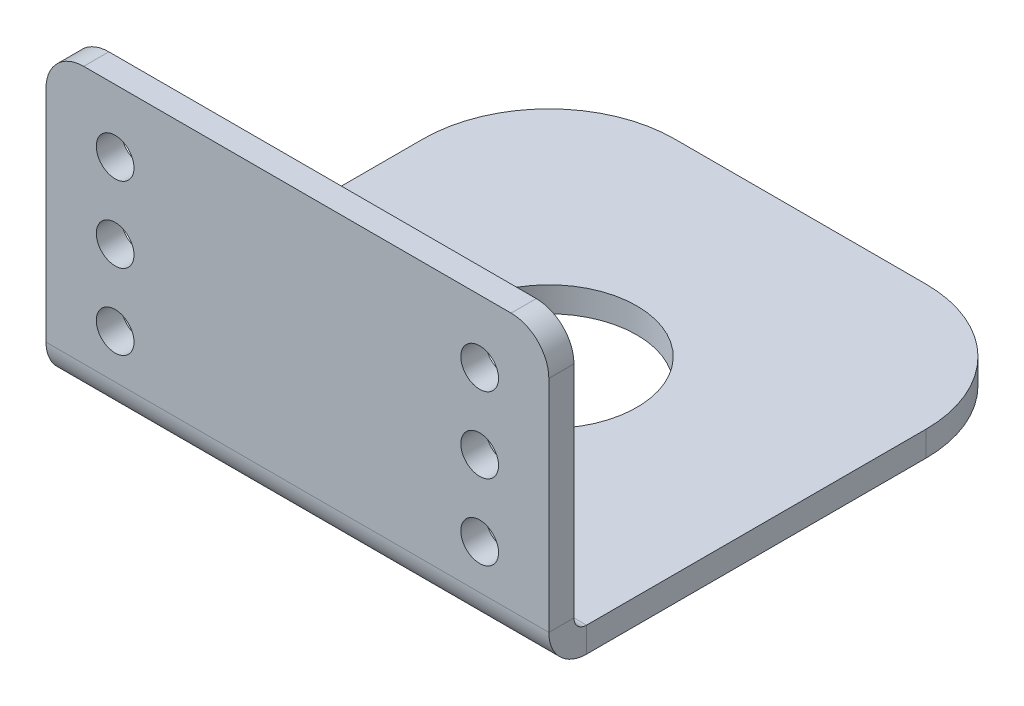
SolidWorks part; units mm, degrees
note: The reader was unsure of these and kept them because the rebuilt part matched: flange length of "Edge-Flange1".
material "AISI 1010 Steel, hot rolled bar"
ref_plane "Front Plane" through (0, 0, 0) normal (0, 0, 1) x (1, 0, 0)
ref_plane "Top Plane" through (0, 0, 0) normal (0, 1, 0) x (1, 0, 0)
ref_plane "Right Plane" through (0, 0, 0) normal (1, 0, 0) x (0, 0, -1)
sketch "Sketch1" plane through (0, 0, 0) normal (0, 1, 0) x (1, 0, 0)
  line L1 (20, -19) -> (-20, -19)
  line L2 (20, -19) -> (20, 19)
  line L3 (20, 19) -> (-20, 19)
  line L4 (-20, -19) -> (-20, 19)
  line L5 (20, -19) -> (-20, 19) construction
  line L6 (20, 19) -> (-20, -19) construction
  circle A0 centre (0, -1) radius 7
  circle A1 centre (0, -10.5) radius 1.5
  point P0 (0, 0)
  dimension "D3" = 14
  dimension "D5" = 3
  dimension "D1" = 40
  dimension "D2" = 38
  dimension "D4" = 20
  dimension "D6" = 10.5
base flange "Base-Flange1" sketch "Sketch1" thickness 2 reverse thickness direction no parameters "D1"=1
edge flange "Edge-Flange1" sketch "Sketch9" flange angle 90 flange length 23.5 flange position material outside bend radius 1 thickness 2 relief rectangular parameters "D6"=10
sketch "Sketch9" plane through (0, 0, 19) normal (0, 0, 1) x (1, 0, 0)
  line L0 (-20, 0) -> (20, 0) construction
  line L1 (-20, 0) -> (20, 0)
  line L2 (-20, 0) -> (-20, 21.5)
  line L3 (-20, 21.5) -> (20, 21.5)
  line L4 (20, 21.5) -> (20, 0)
bend "EdgeBend1" bend radius 1 bend angle 90 parameters "D5"=1
fillet "Fillet1" radius 10 2 edges at (20, -1, -19) (-20, -1, -19)
fillet "Fillet2" radius 3 2 edges at (20, 21.5, 20) (-20, 21.5, 20)
sketch "Sketch10" plane through (0, 0, 19) normal (0, 0, -1) x (-1, 0, 0)
  line L0 (-17, 21.5) -> (17, 21.5) construction
  line L1 (-20, 1) -> (-20, 18.5) construction
  line L2 (0, 0) -> (0, 24.0396) construction
  circle A0 centre (-14.5, 16.5) radius 1.5
  circle A1 centre (-14.5, 10.5) radius 1.5
  circle A2 centre (-14.5, 4.5) radius 1.5
  circle A3 centre (14.5, 4.5) radius 1.5
  circle A4 centre (14.5, 10.5) radius 1.5
  circle A5 centre (14.5, 16.5) radius 1.5
  dimension "D1" = 3
  dimension "D5" = 5.5
  dimension "D6" = 11
  dimension "D2" = 5
  dimension "D3" = 5.5
  dimension "D4" = 3
extrude "Cut-Extrude1" cut sketch "Sketch10" against normal through all normal cut yes
sketch "Bend-Lines1" [suppressed] plane through (0, 0, 0) normal (0, 1, 0) x (1, 0, 0)
sketch "Bounding-Box1" [suppressed] plane through (0, 0, 0) normal (0, 1, 0) x (1, 0, 0)
sheet metal parameters "Sheet-Metal1" thickness 2 parameters "D1"=1
flat pattern "Flat-Pattern1" [suppressed]
sketch "Bend-Lines2" plane through (0, 0, 0) normal (0, 1, 0) x (1, 0, 0)
sketch "Bounding-Box2" [suppressed] plane through (0, 0, 0) normal (0, 1, 0) x (1, 0, 0)
sheet metal parameters "Sheet-Metal2" thickness 2 parameters "D1"=1
flat pattern "Flat-Pattern1" [suppressed]
sketch "Bend-Lines2" plane through (0, 0, 0) normal (0, 1, 0) x (1, 0, 0)
sketch "Bounding-Box2" [suppressed] plane through (0, 0, 0) normal (0, 1, 0) x (1, 0, 0)
bend of the flat pattern "Flatten-<EdgeBend1>1"
sheet metal parameters "Sheet-Metal3" thickness 2 parameters "D1"=1
flat pattern "Flat-Pattern1"
sketch "Bend-Lines2" plane through (0, 0, 0) normal (0, 1, 0) x (1, 0, 0)
  line L0 (-20, -19.5708) -> (20, -19.5708) construction
  line L1 (-20, -19.5708) -> (20, -19.5708) construction
sketch3d "Bounding-Box2" [suppressed]
  line L0 (-20, 19, 0) -> (-20, -41.6416, 0) construction
  line L1 (20, 19, 0) -> (20, -41.6416, 0) construction
  line L2 (-20, 19, 0) -> (20, 19, 0) construction
  line L3 (-20, -41.6416, 0) -> (20, -41.6416, 0) construction
bend of the flat pattern "Flatten-<EdgeBend1>1"
